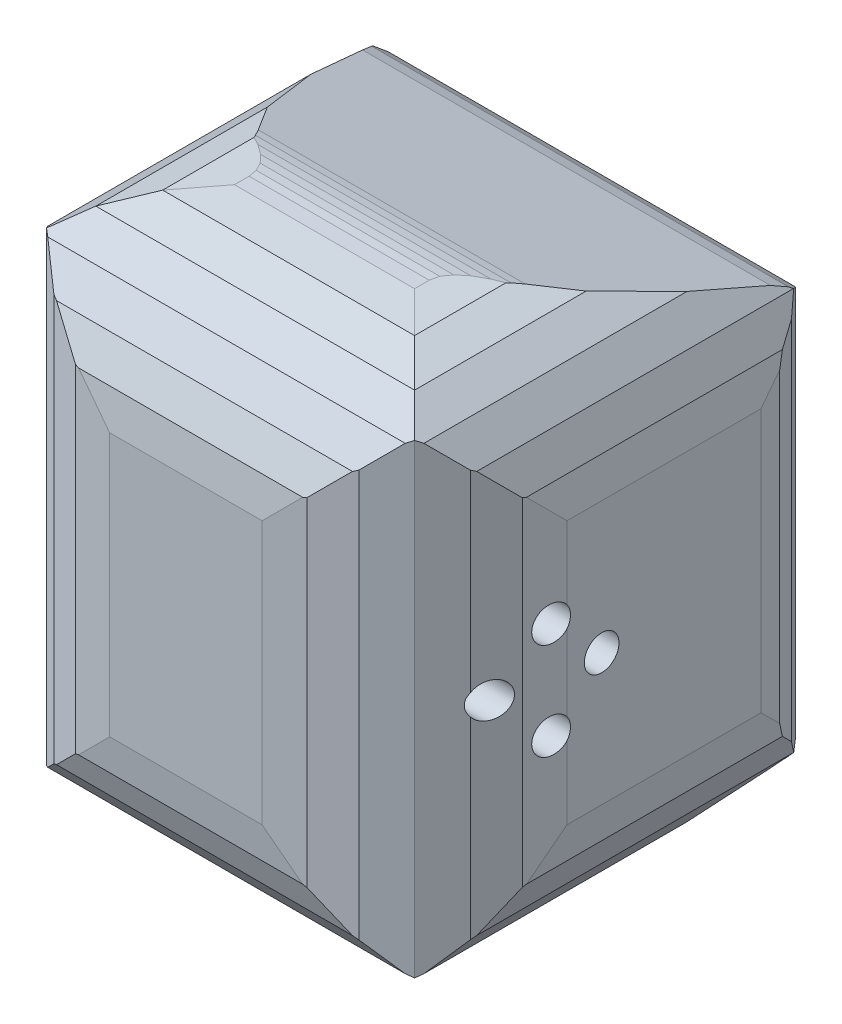
SolidWorks part; units mm, degrees
ref_plane "Front Plane" through (0, 0, 0) normal (0, 0, 1) x (1, 0, 0)
ref_plane "Top Plane" through (0, 0, 0) normal (0, 1, 0) x (1, 0, 0)
ref_plane "Right Plane" through (0, 0, 0) normal (1, 0, 0) x (0, 0, -1)
ref_plane "PX_m33_000" through (-33, 0, 0) normal (1, 0, 0) x (0, 0, -1)
sketch "S_prism1" plane through (-33, 0, 0) normal (1, 0, 0) x (0, 0, -1)
  line L0 (-7.078, -30.163) -> (-5.128, -29.332)
  line L1 (-5.128, -29.332) -> (-3.396, -28.109)
  line L2 (-3.396, -28.109) -> (-1.962, -26.548)
  line L3 (-1.962, -26.548) -> (-0.889, -24.72)
  line L4 (-0.889, -24.72) -> (-0.225, -22.707)
  line L5 (-0.225, -22.707) -> (0, -20.599)
  line L6 (0, -20.599) -> (0, 20.599)
  line L7 (0, 20.599) -> (-0.225, 22.707)
  line L8 (-0.225, 22.707) -> (-0.889, 24.72)
  line L9 (-0.889, 24.72) -> (-1.962, 26.548)
  line L10 (-1.962, 26.548) -> (-3.396, 28.109)
  line L11 (-3.396, 28.109) -> (-5.128, 29.332)
  line L12 (-5.128, 29.332) -> (-7.078, 30.163)
  line L13 (-7.078, 30.163) -> (-32.286, 37.865)
  line L14 (-32.286, 37.865) -> (-33.524, 38.21)
  line L15 (-33.524, 38.21) -> (-34.777, 38.494)
  line L16 (-34.777, 38.494) -> (-36.043, 38.715)
  line L17 (-36.043, 38.715) -> (-37.318, 38.873)
  line L18 (-37.318, 38.873) -> (-38.599, 38.968)
  line L19 (-38.599, 38.968) -> (-39.884, 39)
  line L20 (-39.884, 39) -> (-42, 39)
  line L21 (-42, 39) -> (-47.176, 38.319)
  line L22 (-47.176, 38.319) -> (-52, 36.321)
  line L23 (-52, 36.321) -> (-56.142, 33.142)
  line L24 (-56.142, 33.142) -> (-59.321, 29)
  line L25 (-59.321, 29) -> (-61.319, 24.176)
  line L26 (-61.319, 24.176) -> (-62, 19)
  line L27 (-62, 19) -> (-62, -19)
  line L28 (-62, -19) -> (-61.319, -24.176)
  line L29 (-61.319, -24.176) -> (-59.321, -29)
  line L30 (-59.321, -29) -> (-56.142, -33.142)
  line L31 (-56.142, -33.142) -> (-52, -36.321)
  line L32 (-52, -36.321) -> (-47.176, -38.319)
  line L33 (-47.176, -38.319) -> (-42, -39)
  line L34 (-42, -39) -> (-39.884, -39)
  line L35 (-39.884, -39) -> (-38.599, -38.968)
  line L36 (-38.599, -38.968) -> (-37.318, -38.873)
  line L37 (-37.318, -38.873) -> (-36.043, -38.715)
  line L38 (-36.043, -38.715) -> (-34.777, -38.494)
  line L39 (-34.777, -38.494) -> (-33.524, -38.21)
  line L40 (-33.524, -38.21) -> (-32.286, -37.865)
  line L41 (-32.286, -37.865) -> (-7.078, -30.163)
  dimension "P1" = 7.078
  dimension "P2" = 30.163
  dimension "P3" = 5.128
  dimension "P4" = 29.332
  dimension "P5" = 3.396
  dimension "P6" = 28.109
  dimension "P7" = 1.962
  dimension "P8" = 26.548
  dimension "P9" = 0.889
  dimension "P10" = 24.72
  dimension "P11" = 0.225
  dimension "P12" = 22.707
  dimension "P13" = 20.599
  dimension "P14" = 20.599
  dimension "P15" = 0.225
  dimension "P16" = 22.707
  dimension "P17" = 0.889
  dimension "P18" = 24.72
  dimension "P19" = 1.962
  dimension "P20" = 26.548
  dimension "P21" = 3.396
  dimension "P22" = 28.109
  dimension "P23" = 5.128
  dimension "P24" = 29.332
  dimension "P25" = 7.078
  dimension "P26" = 30.163
  dimension "P27" = 32.286
  dimension "P28" = 37.865
  dimension "P29" = 33.524
  dimension "P30" = 38.21
  dimension "P31" = 34.777
  dimension "P32" = 38.494
  dimension "P33" = 36.043
  dimension "P34" = 38.715
  dimension "P35" = 37.318
  dimension "P36" = 38.873
  dimension "P37" = 38.599
  dimension "P38" = 38.968
  dimension "P39" = 39.884
  dimension "P40" = 39
  dimension "P41" = 42
  dimension "P42" = 39
  dimension "P43" = 47.176
  dimension "P44" = 38.319
  dimension "P45" = 52
  dimension "P46" = 36.321
  dimension "P47" = 56.142
  dimension "P48" = 33.142
  dimension "P49" = 59.321
  dimension "P50" = 29
  dimension "P51" = 61.319
  dimension "P52" = 24.176
  dimension "P53" = 62
  dimension "P54" = 19
  dimension "P55" = 62
  dimension "P56" = 19
  dimension "P57" = 61.319
  dimension "P58" = 24.176
  dimension "P59" = 59.321
  dimension "P60" = 29
  dimension "P61" = 56.142
  dimension "P62" = 33.142
  dimension "P63" = 52
  dimension "P64" = 36.321
  dimension "P65" = 47.176
  dimension "P66" = 38.319
  dimension "P67" = 42
  dimension "P68" = 39
  dimension "P69" = 39.884
  dimension "P70" = 39
  dimension "P71" = 38.599
  dimension "P72" = 38.968
  dimension "P73" = 37.318
  dimension "P74" = 38.873
  dimension "P75" = 36.043
  dimension "P76" = 38.715
  dimension "P77" = 34.777
  dimension "P78" = 38.494
  dimension "P79" = 33.524
  dimension "P80" = 38.21
  dimension "P81" = 32.286
  dimension "P82" = 37.865
extrude "Boss_1" add sketch "S_prism1" along normal blind 66
ref_plane "PY_m40_000" through (0, -40, 0) normal (0, 1, 0) x (1, 0, 0)
sketch "S_pcut2" plane through (0, -40, 0) normal (0, 1, 0) x (1, 0, 0)
  line L0 (33.6, -62.6) -> (11, -62.6)
  line L1 (11, -62.6) -> (11, -62)
  line L2 (11, -62) -> (16.694, -61.25)
  line L3 (16.694, -61.25) -> (22, -59.053)
  line L4 (22, -59.053) -> (26.556, -55.556)
  line L5 (26.556, -55.556) -> (30.053, -51)
  line L6 (30.053, -51) -> (32.25, -45.694)
  line L7 (32.25, -45.694) -> (33, -40)
  line L8 (33, -40) -> (33.6, -40)
  line L9 (33.6, -40) -> (33.6, -62.6)
  dimension "P1" = 33.6
  dimension "P2" = 62.6
  dimension "P3" = 11
  dimension "P4" = 62.6
  dimension "P5" = 11
  dimension "P6" = 62
  dimension "P7" = 16.694
  dimension "P8" = 61.25
  dimension "P9" = 22
  dimension "P10" = 59.053
  dimension "P11" = 26.556
  dimension "P12" = 55.556
  dimension "P13" = 30.053
  dimension "P14" = 51
  dimension "P15" = 32.25
  dimension "P16" = 45.694
  dimension "P17" = 33
  dimension "P18" = 40
  dimension "P19" = 33.6
  dimension "P20" = 40
extrude "Cut_2" cut sketch "S_pcut2" along normal blind 80
sketch "S_pcut3" plane through (0, -40, 0) normal (0, 1, 0) x (1, 0, 0)
  line L0 (-33.6, -62.6) -> (-11, -62.6)
  line L1 (-11, -62.6) -> (-11, -62)
  line L2 (-11, -62) -> (-16.694, -61.25)
  line L3 (-16.694, -61.25) -> (-22, -59.053)
  line L4 (-22, -59.053) -> (-26.556, -55.556)
  line L5 (-26.556, -55.556) -> (-30.053, -51)
  line L6 (-30.053, -51) -> (-32.25, -45.694)
  line L7 (-32.25, -45.694) -> (-33, -40)
  line L8 (-33, -40) -> (-33.6, -40)
  line L9 (-33.6, -40) -> (-33.6, -62.6)
  dimension "P1" = 33.6
  dimension "P2" = 62.6
  dimension "P3" = 11
  dimension "P4" = 62.6
  dimension "P5" = 11
  dimension "P6" = 62
  dimension "P7" = 16.694
  dimension "P8" = 61.25
  dimension "P9" = 22
  dimension "P10" = 59.053
  dimension "P11" = 26.556
  dimension "P12" = 55.556
  dimension "P13" = 30.053
  dimension "P14" = 51
  dimension "P15" = 32.25
  dimension "P16" = 45.694
  dimension "P17" = 33
  dimension "P18" = 40
  dimension "P19" = 33.6
  dimension "P20" = 40
extrude "Cut_3" cut sketch "S_pcut3" along normal blind 80
sketch "S_pcut4" plane through (0, -40, 0) normal (0, 1, 0) x (1, 0, 0)
  line L0 (33.6, 0.6) -> (21, 0.6)
  line L1 (21, 0.6) -> (21, 0)
  line L2 (21, 0) -> (24.106, -0.409)
  line L3 (24.106, -0.409) -> (27, -1.608)
  line L4 (27, -1.608) -> (29.485, -3.515)
  line L5 (29.485, -3.515) -> (31.392, -6)
  line L6 (31.392, -6) -> (32.591, -8.894)
  line L7 (32.591, -8.894) -> (33, -12)
  line L8 (33, -12) -> (33.6, -12)
  line L9 (33.6, -12) -> (33.6, 0.6)
  dimension "P1" = 33.6
  dimension "P2" = 0.6
  dimension "P3" = 21
  dimension "P4" = 0.6
  dimension "P5" = 21
  dimension "P6" = 24.106
  dimension "P7" = 0.409
  dimension "P8" = 27
  dimension "P9" = 1.608
  dimension "P10" = 29.485
  dimension "P11" = 3.515
  dimension "P12" = 31.392
  dimension "P13" = 6
  dimension "P14" = 32.591
  dimension "P15" = 8.894
  dimension "P16" = 33
  dimension "P17" = 12
  dimension "P18" = 33.6
  dimension "P19" = 12
extrude "Cut_4" cut sketch "S_pcut4" along normal blind 80
sketch "S_pcut5" plane through (0, -40, 0) normal (0, 1, 0) x (1, 0, 0)
  line L0 (-33.6, 0.6) -> (-21, 0.6)
  line L1 (-21, 0.6) -> (-21, 0)
  line L2 (-21, 0) -> (-24.106, -0.409)
  line L3 (-24.106, -0.409) -> (-27, -1.608)
  line L4 (-27, -1.608) -> (-29.485, -3.515)
  line L5 (-29.485, -3.515) -> (-31.392, -6)
  line L6 (-31.392, -6) -> (-32.591, -8.894)
  line L7 (-32.591, -8.894) -> (-33, -12)
  line L8 (-33, -12) -> (-33.6, -12)
  line L9 (-33.6, -12) -> (-33.6, 0.6)
  dimension "P1" = 33.6
  dimension "P2" = 0.6
  dimension "P3" = 21
  dimension "P4" = 0.6
  dimension "P5" = 21
  dimension "P6" = 24.106
  dimension "P7" = 0.409
  dimension "P8" = 27
  dimension "P9" = 1.608
  dimension "P10" = 29.485
  dimension "P11" = 3.515
  dimension "P12" = 31.392
  dimension "P13" = 6
  dimension "P14" = 32.591
  dimension "P15" = 8.894
  dimension "P16" = 33
  dimension "P17" = 12
  dimension "P18" = 33.6
  dimension "P19" = 12
extrude "Cut_5" cut sketch "S_pcut5" along normal blind 80
ref_plane "PZ_m0_100" through (0, 0, -0.1) normal (0, 0, 1) x (1, 0, 0)
sketch "S_pcut6" plane through (0, 0, -0.1) normal (0, 0, 1) x (1, 0, 0)
  line L0 (33.6, 39.6) -> (13, 39.6)
  line L1 (13, 39.6) -> (13, 39)
  line L2 (13, 39) -> (18.176, 38.319)
  line L3 (18.176, 38.319) -> (23, 36.321)
  line L4 (23, 36.321) -> (27.142, 33.142)
  line L5 (27.142, 33.142) -> (30.321, 29)
  line L6 (30.321, 29) -> (32.319, 24.176)
  line L7 (32.319, 24.176) -> (33, 19)
  line L8 (33, 19) -> (33.6, 19)
  line L9 (33.6, 19) -> (33.6, 39.6)
  dimension "P1" = 33.6
  dimension "P2" = 39.6
  dimension "P3" = 13
  dimension "P4" = 39.6
  dimension "P5" = 13
  dimension "P6" = 39
  dimension "P7" = 18.176
  dimension "P8" = 38.319
  dimension "P9" = 23
  dimension "P10" = 36.321
  dimension "P11" = 27.142
  dimension "P12" = 33.142
  dimension "P13" = 30.321
  dimension "P14" = 29
  dimension "P15" = 32.319
  dimension "P16" = 24.176
  dimension "P17" = 33
  dimension "P18" = 19
  dimension "P19" = 33.6
  dimension "P20" = 19
extrude "Cut_6" cut sketch "S_pcut6" along normal blind 62.2
sketch "S_pcut7" plane through (0, 0, -0.1) normal (0, 0, 1) x (1, 0, 0)
  line L0 (33.6, -39.6) -> (13, -39.6)
  line L1 (13, -39.6) -> (13, -39)
  line L2 (13, -39) -> (18.176, -38.319)
  line L3 (18.176, -38.319) -> (23, -36.321)
  line L4 (23, -36.321) -> (27.142, -33.142)
  line L5 (27.142, -33.142) -> (30.321, -29)
  line L6 (30.321, -29) -> (32.319, -24.176)
  line L7 (32.319, -24.176) -> (33, -19)
  line L8 (33, -19) -> (33.6, -19)
  line L9 (33.6, -19) -> (33.6, -39.6)
  dimension "P1" = 33.6
  dimension "P2" = 39.6
  dimension "P3" = 13
  dimension "P4" = 39.6
  dimension "P5" = 13
  dimension "P6" = 39
  dimension "P7" = 18.176
  dimension "P8" = 38.319
  dimension "P9" = 23
  dimension "P10" = 36.321
  dimension "P11" = 27.142
  dimension "P12" = 33.142
  dimension "P13" = 30.321
  dimension "P14" = 29
  dimension "P15" = 32.319
  dimension "P16" = 24.176
  dimension "P17" = 33
  dimension "P18" = 19
  dimension "P19" = 33.6
  dimension "P20" = 19
extrude "Cut_7" cut sketch "S_pcut7" along normal blind 62.2
sketch "S_pcut8" plane through (0, 0, -0.1) normal (0, 0, 1) x (1, 0, 0)
  line L0 (-33.6, 39.6) -> (-13, 39.6)
  line L1 (-13, 39.6) -> (-13, 39)
  line L2 (-13, 39) -> (-18.176, 38.319)
  line L3 (-18.176, 38.319) -> (-23, 36.321)
  line L4 (-23, 36.321) -> (-27.142, 33.142)
  line L5 (-27.142, 33.142) -> (-30.321, 29)
  line L6 (-30.321, 29) -> (-32.319, 24.176)
  line L7 (-32.319, 24.176) -> (-33, 19)
  line L8 (-33, 19) -> (-33.6, 19)
  line L9 (-33.6, 19) -> (-33.6, 39.6)
  dimension "P1" = 33.6
  dimension "P2" = 39.6
  dimension "P3" = 13
  dimension "P4" = 39.6
  dimension "P5" = 13
  dimension "P6" = 39
  dimension "P7" = 18.176
  dimension "P8" = 38.319
  dimension "P9" = 23
  dimension "P10" = 36.321
  dimension "P11" = 27.142
  dimension "P12" = 33.142
  dimension "P13" = 30.321
  dimension "P14" = 29
  dimension "P15" = 32.319
  dimension "P16" = 24.176
  dimension "P17" = 33
  dimension "P18" = 19
  dimension "P19" = 33.6
  dimension "P20" = 19
extrude "Cut_8" cut sketch "S_pcut8" along normal blind 62.2
sketch "S_pcut9" plane through (0, 0, -0.1) normal (0, 0, 1) x (1, 0, 0)
  line L0 (-33.6, -39.6) -> (-13, -39.6)
  line L1 (-13, -39.6) -> (-13, -39)
  line L2 (-13, -39) -> (-18.176, -38.319)
  line L3 (-18.176, -38.319) -> (-23, -36.321)
  line L4 (-23, -36.321) -> (-27.142, -33.142)
  line L5 (-27.142, -33.142) -> (-30.321, -29)
  line L6 (-30.321, -29) -> (-32.319, -24.176)
  line L7 (-32.319, -24.176) -> (-33, -19)
  line L8 (-33, -19) -> (-33.6, -19)
  line L9 (-33.6, -19) -> (-33.6, -39.6)
  dimension "P1" = 33.6
  dimension "P2" = 39.6
  dimension "P3" = 13
  dimension "P4" = 39.6
  dimension "P5" = 13
  dimension "P6" = 39
  dimension "P7" = 18.176
  dimension "P8" = 38.319
  dimension "P9" = 23
  dimension "P10" = 36.321
  dimension "P11" = 27.142
  dimension "P12" = 33.142
  dimension "P13" = 30.321
  dimension "P14" = 29
  dimension "P15" = 32.319
  dimension "P16" = 24.176
  dimension "P17" = 33
  dimension "P18" = 19
  dimension "P19" = 33.6
  dimension "P20" = 19
extrude "Cut_9" cut sketch "S_pcut9" along normal blind 62.2
ref_plane "PZ_p4_000" through (0, 0, 4) normal (0, 0, 1) x (1, 0, 0)
sketch "S_cut10" plane through (0, 0, 4) normal (0, 0, 1) x (1, 0, 0)
  line L0 (-26, -24) -> (26, -24)
  line L1 (26, -24) -> (26, 24)
  line L2 (26, 24) -> (-26, 24)
  line L3 (-26, 24) -> (-26, -24)
  dimension "P1" = 26
  dimension "P2" = 24
  dimension "P3" = 26
  dimension "P4" = 24
  dimension "P5" = 26
  dimension "P6" = 24
  dimension "P7" = 26
  dimension "P8" = 24
extrude "Pocket_10" cut sketch "S_cut10" along normal blind 12.1
ref_plane "PZ_p16_000" through (0, 0, 16) normal (0, 0, 1) x (1, 0, 0)
sketch "S_cut11" plane through (0, 0, 16) normal (0, 0, 1) x (1, 0, 0)
  line L0 (-26, -30) -> (26, -30)
  line L1 (26, -30) -> (26, 30)
  line L2 (26, 30) -> (-26, 30)
  line L3 (-26, 30) -> (-26, -30)
  dimension "P1" = 26
  dimension "P2" = 30
  dimension "P3" = 26
  dimension "P4" = 30
  dimension "P5" = 26
  dimension "P6" = 30
  dimension "P7" = 26
  dimension "P8" = 30
extrude "Pocket_11" cut sketch "S_cut11" along normal blind 36
ref_plane "PZ_p51_900" through (0, 0, 51.9) normal (0, 0, 1) x (1, 0, 0)
sketch "S_cut12" plane through (0, 0, 51.9) normal (0, 0, 1) x (1, 0, 0)
  line L0 (-18, -24) -> (18, -24)
  line L1 (18, -24) -> (18, 24)
  line L2 (18, 24) -> (-18, 24)
  line L3 (-18, 24) -> (-18, -24)
  dimension "P1" = 18
  dimension "P2" = 24
  dimension "P3" = 18
  dimension "P4" = 24
  dimension "P5" = 18
  dimension "P6" = 24
  dimension "P7" = 18
  dimension "P8" = 24
extrude "Pocket_12" cut sketch "S_cut12" along normal blind 6.1
sketch "S_cut13" plane through (0, 0, 16) normal (0, 0, 1) x (1, 0, 0)
  line L0 (-33.1, -16) -> (-25.9, -16)
  line L1 (-25.9, -16) -> (-25.9, 16)
  line L2 (-25.9, 16) -> (-33.1, 16)
  line L3 (-33.1, 16) -> (-33.1, -16)
  dimension "P1" = 33.1
  dimension "P2" = 16
  dimension "P3" = 25.9
  dimension "P4" = 16
  dimension "P5" = 25.9
  dimension "P6" = 16
  dimension "P7" = 33.1
  dimension "P8" = 16
extrude "Pocket_13" cut sketch "S_cut13" along normal blind 28
sketch "S_hole14" plane through (0, 0, -0.1) normal (0, 0, 1) x (1, 0, 0)
  circle A0 centre (-18, 0) radius 4
  dimension "D1_S_hole14" = 8
  dimension "P2" = 18
extrude "Hole_14" cut sketch "S_hole14" along normal blind 4.2
ref_plane "PX_p25_900" through (25.9, 0, 0) normal (1, 0, 0) x (0, 0, -1)
sketch "S_hole15" plane through (25.9, 0, 0) normal (1, 0, 0) x (0, 0, -1)
  circle A0 centre (-49, 0) radius 2.5
  dimension "D1_S_hole15" = 5
  dimension "P2" = 49
extrude "Hole_15" cut sketch "S_hole15" along normal blind 7.2
sketch "S_hole16" plane through (25.9, 0, 0) normal (1, 0, 0) x (0, 0, -1)
  circle A0 centre (-42, 7) radius 2.5
  dimension "D1_S_hole16" = 5
  dimension "P2" = 42
  dimension "P3" = 7
extrude "Hole_16" cut sketch "S_hole16" along normal blind 7.2
sketch "S_hole17" plane through (25.9, 0, 0) normal (1, 0, 0) x (0, 0, -1)
  circle A0 centre (-42, -7) radius 2.5
  dimension "D1_S_hole17" = 5
  dimension "P2" = 42
  dimension "P3" = 7
extrude "Hole_17" cut sketch "S_hole17" along normal blind 7.2
sketch "S_hole18" plane through (25.9, 0, 0) normal (1, 0, 0) x (0, 0, -1)
  circle A0 centre (-35, 0) radius 2.5
  dimension "D1_S_hole18" = 5
  dimension "P2" = 35
extrude "Hole_18" cut sketch "S_hole18" along normal blind 7.2
sketch "S_hole19" plane through (0, 0, -0.1) normal (0, 0, 1) x (1, 0, 0)
  circle A0 centre (0, 0) radius 3
  dimension "D1_S_hole19" = 6
extrude "Hole_19" cut sketch "S_hole19" along normal blind 4.2
sketch "S_hole20" plane through (0, 0, -0.1) normal (0, 0, 1) x (1, 0, 0)
  circle A0 centre (7, 0) radius 1.35
  dimension "D1_S_hole20" = 2.7
  dimension "P2" = 7
extrude "Hole_20" cut sketch "S_hole20" along normal blind 4.2
sketch "S_hole21" plane through (0, 0, -0.1) normal (0, 0, 1) x (1, 0, 0)
  circle A0 centre (0, 7) radius 1.35
  dimension "D1_S_hole21" = 2.7
  dimension "P2" = 7
extrude "Hole_21" cut sketch "S_hole21" along normal blind 4.2
sketch "S_hole22" plane through (0, 0, -0.1) normal (0, 0, 1) x (1, 0, 0)
  circle A0 centre (-7, 0) radius 1.35
  dimension "D1_S_hole22" = 2.7
  dimension "P2" = 7
extrude "Hole_22" cut sketch "S_hole22" along normal blind 4.2
sketch "S_hole23" plane through (0, 0, -0.1) normal (0, 0, 1) x (1, 0, 0)
  circle A0 centre (0, -7) radius 1.35
  dimension "D1_S_hole23" = 2.7
  dimension "P2" = 7
extrude "Hole_23" cut sketch "S_hole23" along normal blind 4.2
equation "\"plate_t\" = 3"
equation "\"clearance\" = 0.4"
